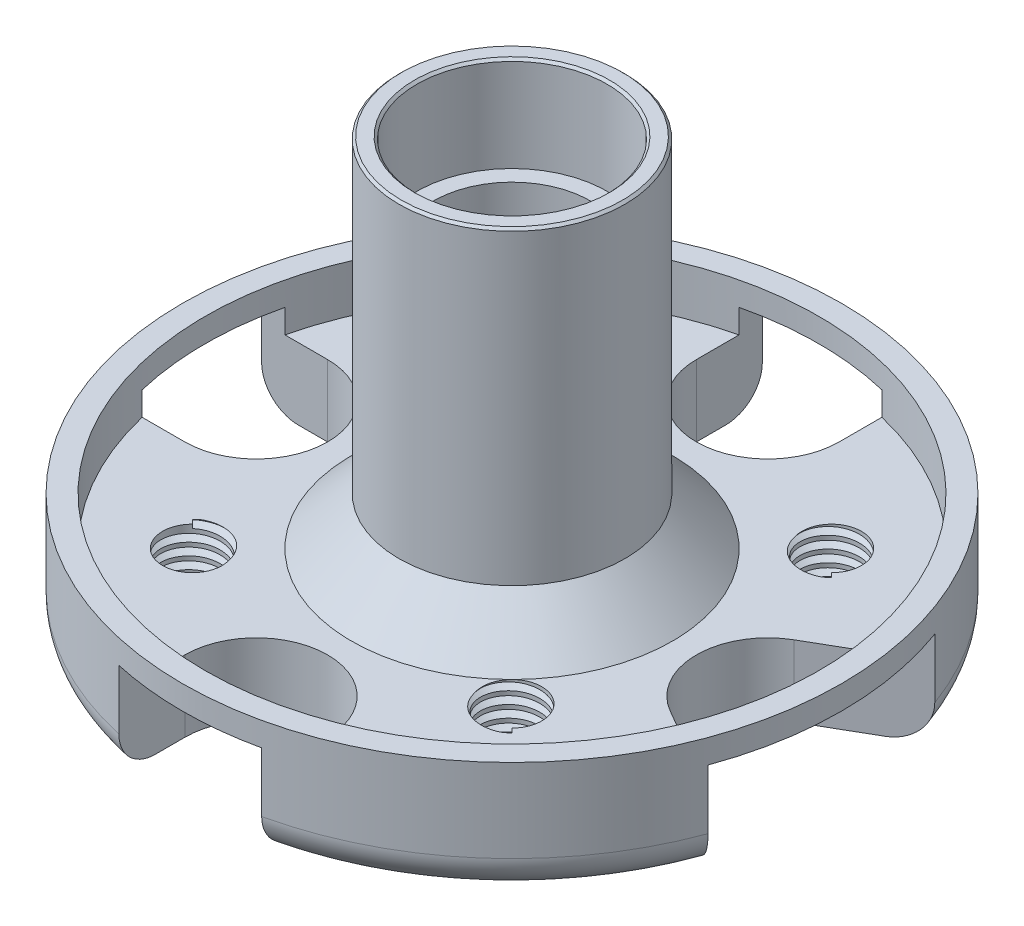
SolidWorks part; units mm, degrees
material "3003-H16"
ref_plane "Plano frontal" through (0, 0, 0) normal (0, 0, 1) x (1, 0, 0)
ref_plane "Plano superior" through (0, 0, 0) normal (0, 1, 0) x (1, 0, 0)
ref_plane "Plano direito" through (0, 0, 0) normal (1, 0, 0) x (0, 0, -1)
sketch "Esboço1" plane through (0, 0, 0) normal (0, 0, 1) x (1, 0, 0)
  line L0 (0, 10.8061) -> (0, 0) construction
  line L1 (0, 0) -> (13.85, 0) construction
  line L2 (4.1, 0) -> (12.35, 0)
  line L3 (13.85, 1.5) -> (13.85, 5)
  line L4 (13.85, 5) -> (12.9, 5)
  line L5 (12.9, 5) -> (12.9, 3)
  line L6 (12.9, 3) -> (6.75, 3)
  line L7 (6.75, 3) -> (4.75, 5)
  line L8 (4.75, 5) -> (4.75, 17.9)
  line L9 (4.65, 18) -> (4.1, 18)
  line L10 (4, 17.9) -> (4, 14)
  line L11 (4, 14) -> (3.3, 14)
  line L12 (3.3, 14) -> (3.3, 4)
  line L13 (3.3, 4) -> (4, 4)
  line L14 (4, 4) -> (4, 0.1)
  line L15 (4, 0.1) -> (4.1, 0)
  line L16 (4.75, 17.9) -> (4.65, 18)
  line L17 (4.1, 18) -> (4, 17.9)
  arc A0 (13.85, 1.5) -> (12.35, 0) centre (12.35, 1.5) cw
  point P5 (4.75, 18)
  point P12 (4, 18)
  point P17 (4, 0)
  dimension "D14" = 1.5
  dimension "D1" = 18
  dimension "D2" = 6.6
  dimension "D3" = 8
  dimension "D4" = 8
  dimension "D5" = 9.5
  dimension "D6" = 27.7
  dimension "D7" = 4
  dimension "D8" = 3
  dimension "D9" = 5
  dimension "D10" = 4
  dimension "D11" = 45
  dimension "D12" = 0.95
  dimension "D13" = 13
  dimension "D15" = 0.1
  dimension "D16" = 45
  dimension "D17" = 0.1
  dimension "D18" = 45
  dimension "D19" = 0.1
  dimension "D20" = 45
revolve "Revolução1" add sketch "Esboço1" angle 360 about L0
sketch "Esboço2" plane through (0, 0, 0) normal (0, -1, 0) x (1, 0, 0)
  line L0 (0, 0) -> (0, 15.2486) construction
  line L1 (3, 10.75) -> (3, 13.5212)
  line L2 (-3, 10.75) -> (-3, 13.5212)
  circle A0 centre (0, 0) radius 7.75 construction
  circle A1 centre (0, 0) radius 13.85 construction
  arc A2 (3, 13.5212) -> (-3, 13.5212) centre (0, 0) ccw
  arc A3 (-3, 10.75) -> (3, 10.75) centre (0, 10.75) ccw
  dimension "D1" = 15.5
  dimension "D2" = 3
extrude "Corte-extrusão1" cut sketch "Esboço2" against normal blind 4
pattern_circular "PadrãoCircular1" count 4 over 360 about axis through (0, 0, 0) along (0, 1, 0) of "Corte-extrusão1"
sketch "Esboço3" plane through (0, 0, 0) normal (0, -1, 0) x (1, 0, 0)
  line L0 (9.25, 2.5981) -> (18.7195, 8.0653)
  line L1 (18.7195, 8.0653) -> (18.7195, -8.0653)
  line L2 (18.7195, -8.0653) -> (9.25, -2.5981)
  line L3 (10.75, 0) -> (20.0882, 0) construction
  arc A0 (10.75, 3) -> (10.75, -3) centre (10.75, 0) ccw construction
  arc A1 (9.25, 2.5981) -> (9.25, -2.5981) centre (10.75, 0) ccw
  dimension "D1" = 60
extrude "Corte-extrusão2" cut sketch "Esboço3" against normal blind 4
sketch "Esboço4" plane through (0, 0, 0) normal (0, -1, 0) x (1, 0, 0)
  line L0 (0, 0) -> (11.7522, 0) construction
  line L1 (0, 0) -> (0, 11.9019) construction
  line L2 (-5.6569, -5.6569) -> (5.6569, 5.6569) construction
  line L3 (-6.7175, 6.7175) -> (6.7175, -6.7175) construction
  circle A0 centre (0, 0) radius 8 construction
  circle A1 centre (0, 0) radius 9.5 construction
  point P9 (0, 0)
  point P12 (0, 0)
  dimension "D1" = 16
  dimension "D2" = 19
  dimension "D3" = 45
hole_wizard "Furo roscado de M31" positions "3DSketch1" profile "Esboço5" tap size "M3" standard "ISO" end condition up to next
sketch3d "3DSketch1"
  point P0 (5.6569, 0, 5.6569)
  point P3 (6.7175, 0, -6.7175)
  point P6 (-5.6569, 0, -5.6569)
  point P9 (-6.7175, 0, 6.7175)
sketch "Esboço5" plane through (5.6569, 0, 5.6569) normal (1, 0, 0) x (0, 0, -1)
  line L0 (0, 0) -> (0, 3)
  line L1 (0, 3) -> (1.25, 3)
  line L2 (1.25, 3) -> (1.25, 0.5)
  line L3 (1.25, 0.5) -> (1.75, 0)
  line L5 (1.75, 0) -> (0, 0)
  line L6 (-1.25, 0.5) -> (-1.75, 0) construction
  line L11 (0, -6.35) -> (0, 107.95) construction
  dimension "Thru Tap Drill Dia." = 2.5
  dimension "Thru Tap Drill Depth" = 3
  dimension "Near C'Sink Dia." = 3.5
  dimension "Near C'Sink Angle" = 90
ref_plane "Plano1" through (0, 0, 0) normal (0.7071, 0, 0.7071) x (0, 1, 0)
sketch "Esboço7" plane through (0, 3, 0) normal (0, 1, 0) x (1, 0, 0)
  circle A0 centre (6.7175, 6.7175) radius 1.5
  dimension "D1" = 3
curve "Hélice/Espiral1" pitch 0.5 height 3.5 turns 7
sketch "Esboço8" plane through (0, 0, 0) normal (0.7071, 0, 0.7071) x (0, 1, 0)
  line L0 (-0.375, -9.815) -> (-0.375, -12.6021) construction
  line L1 (-0.3905, -11) -> (-0.3595, -11)
  line L2 (-0.3595, -11) -> (-0.094, -10.5401)
  line L3 (-0.094, -10.5401) -> (-0.125, -10.5401)
  line L4 (-0.125, -10.5401) -> (-0.125, -10.4401)
  line L5 (-0.125, -10.4401) -> (-0.625, -10.4401)
  line L6 (-0.625, -10.5401) -> (-0.625, -10.4401)
  line L7 (-0.656, -10.5401) -> (-0.625, -10.5401)
  line L8 (-0.3905, -11) -> (-0.656, -10.5401)
  point P8 (-0.375, -10.4401)
  point P16 (-0.375, -11)
  dimension "D1" = 0.5
  dimension "D2" = 0.031
  dimension "D3" = 0.1
  dimension "D4" = 60
  dimension "D5" = 0.031
sweep "Varredura de corte8" cut profiles "Esboço8" path "Hélice/Espiral1"
pattern_circular "PadrãoCircular2" count 2 over 360 about axis through (0, 10.8061, 0) along (0, 1, 0) of "Varredura de corte8"
ref_plane "Plano3" through (0, 0, 0) normal (0.7071, 0, -0.7071) x (0, 1, 0)
sketch "Esboço10" plane through (0, 3, 0) normal (0, 1, 0) x (1, 0, 0)
  circle A0 centre (5.6569, -5.6569) radius 1.5
  dimension "D1" = 3
curve "Hélice/Espiral2" pitch 0.5 height 3.5 turns 7
sketch "Esboço11" plane through (0, 0, 0) normal (0.7071, 0, -0.7071) x (0, 1, 0)
  line L0 (-0.5, 10.7273) -> (-0.5, 7.9997) construction
  line L4 (-0.75, 9.1475) -> (-0.75, 9.0475)
  line L5 (-0.75, 9.0475) -> (-0.25, 9.0475)
  line L6 (-0.25, 9.1475) -> (-0.25, 9.0475)
  line L14 (-0.75, 9.1475) -> (-0.719, 9.1475)
  line L15 (-0.719, 9.1475) -> (-0.5155, 9.5)
  line L16 (-0.5155, 9.5) -> (-0.4845, 9.5)
  line L17 (-0.4845, 9.5) -> (-0.281, 9.1475)
  line L18 (-0.281, 9.1475) -> (-0.25, 9.1475)
  point P3 (-0.5, 9.5)
  point P9 (-0.5, 9.0475)
  dimension "D1" = 0.031
  dimension "D2" = 0.5
  dimension "D3" = 0.1
  dimension "D4" = 60
sweep "Varredura de corte14" cut profiles "Esboço11" path "Hélice/Espiral2"
pattern_circular "PadrãoCircular3" count 2 over 360 about axis through (0, 10.8061, 0) along (0, 1, 0) of "Varredura de corte14"
equation "\"D5@Esboço8\"=\"D2@Esboço8\""
